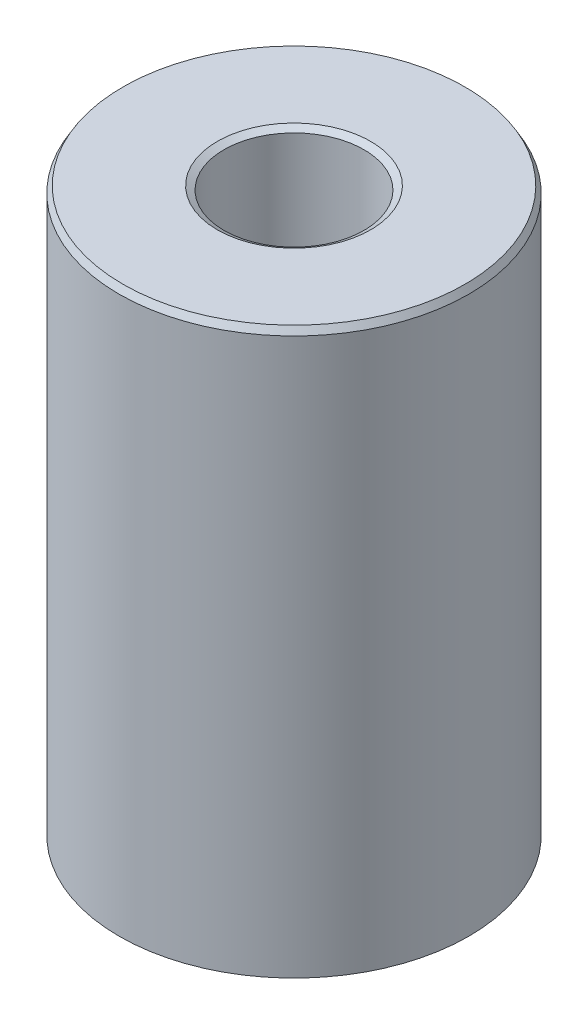
SolidWorks part; units mm, degrees
ref_plane "Front Plane" through (0, 0, 0) normal (0, 0, 1) x (1, 0, 0)
ref_plane "Top Plane" through (0, 0, 0) normal (0, 1, 0) x (1, 0, 0)
ref_plane "Right Plane" through (0, 0, 0) normal (1, 0, 0) x (0, 0, -1)
sketch "Sketch1" plane through (0, 0, 0) normal (0, 1, 0) x (1, 0, 0)
  circle A0 centre (0, 0) radius 7.5
  dimension "SLEEVE_OD" = 15
extrude "Boss-Extrude1" add sketch "Sketch1" along normal blind 24.3066
sketch "Sketch2" plane through (0, 0, 0) normal (0, 1, 0) x (1, 0, 0)
  circle A0 centre (0, 0) radius 3.0032
  dimension "BORE_D" = 6.0063
extrude "Cut-Extrude1" cut sketch "Sketch2" along normal through all
chamfer "Chamfer1" distance 0.2859 angle 30 4 edges at (0, 24.3066, 3.0032) (0, 0, 3.0032) (0, 0, 7.5) (0, 24.3066, 7.5) first distance on face at (0, 24.3066, 3.0032) first distance on face at (0, 0, 3.0032) first distance on face at (0, 24.3066, 7.5)
